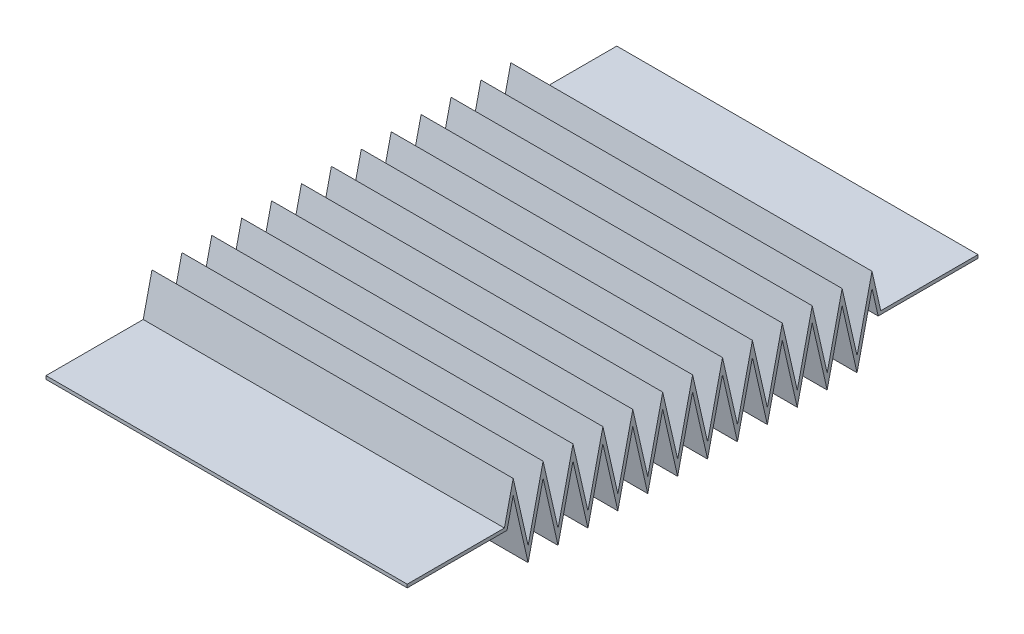
SolidWorks part; units mm, degrees
ref_plane "Front Plane" through (0, 0, 0) normal (0, 0, 1) x (1, 0, 0)
ref_plane "Top Plane" through (0, 0, 0) normal (0, 1, 0) x (1, 0, 0)
ref_plane "Right Plane" through (0, 0, 0) normal (1, 0, 0) x (0, 0, -1)
sketch "Sketch2" plane through (0, 0, 0) normal (0, 0, 1) x (1, 0, 0)
  line L1 (-27.5, 10) -> (27.5, 10)
  line L2 (-27.5, 10) -> (-27.5, 0)
  line L3 (-27.5, 0) -> (27.5, 0)
  line L4 (27.5, 10) -> (27.5, 0)
  point P4 (0, 0)
  dimension "D1" = 10
  dimension "D2" = 55
sketch "Sketch3" plane through (0, 0, 0) normal (1, 0, 0) x (0, 0, -1)
  line L0 (0, 10) -> (86.9132, 10) construction
  line L1 (0, 0) -> (86.9132, 0) construction
  line L3 (15, 5) -> (16.1383, 10)
  line L4 (16.1383, 10) -> (18.4148, 0)
  line L5 (18.4148, 0) -> (20.6913, 10)
  line L6 (20.6913, 10) -> (22.9678, 0)
  line L7 (22.9678, 0) -> (25.2444, 10)
  line L8 (25.2444, 10) -> (27.5209, 0)
  line L9 (27.5209, 0) -> (29.7974, 10)
  line L10 (29.7974, 10) -> (32.074, 0)
  line L11 (32.074, 0) -> (34.3505, 10)
  line L12 (34.3505, 10) -> (36.627, 0)
  line L13 (36.627, 0) -> (38.9035, 10)
  line L14 (38.9035, 10) -> (41.1801, 0)
  line L15 (41.1801, 0) -> (43.4566, 10)
  line L16 (43.4566, 10) -> (45.7331, 0)
  line L17 (45.7331, 0) -> (48.0097, 10)
  line L18 (48.0097, 10) -> (50.2862, 0)
  line L19 (0, 10) -> (0, 0) construction
  line L20 (50.2862, 0) -> (52.5627, 10)
  line L21 (52.5627, 10) -> (54.8392, 0)
  line L22 (54.8392, 0) -> (57.1158, 10)
  line L23 (57.1158, 10) -> (59.3923, 0)
  line L24 (59.3923, 0) -> (61.6688, 10)
  line L25 (61.6688, 10) -> (63.9454, 0)
  line L26 (63.9454, 0) -> (66.2219, 10)
  line L27 (66.2219, 10) -> (68.4984, 0)
  line L28 (68.4984, 0) -> (70.7749, 10)
  line L29 (70.7749, 10) -> (71.9132, 5)
  line L30 (86.9132, 10) -> (86.9132, 0) construction
  line L31 (15, 5) -> (0, 5)
  line L32 (71.9132, 5) -> (86.9132, 5)
  line L33 (86.9132, 4.75) -> (86.9132, 22.75) construction
  point P24 (15, 5)
  point P25 (25.4202, 10)
  dimension "D2" = 15
  dimension "D1" = 10
  dimension "D3" = 15
extrude "Extrude-Thin1" add sketch "Sketch3" against normal mid plane 55 thin thin type mid plane wall 0.5
